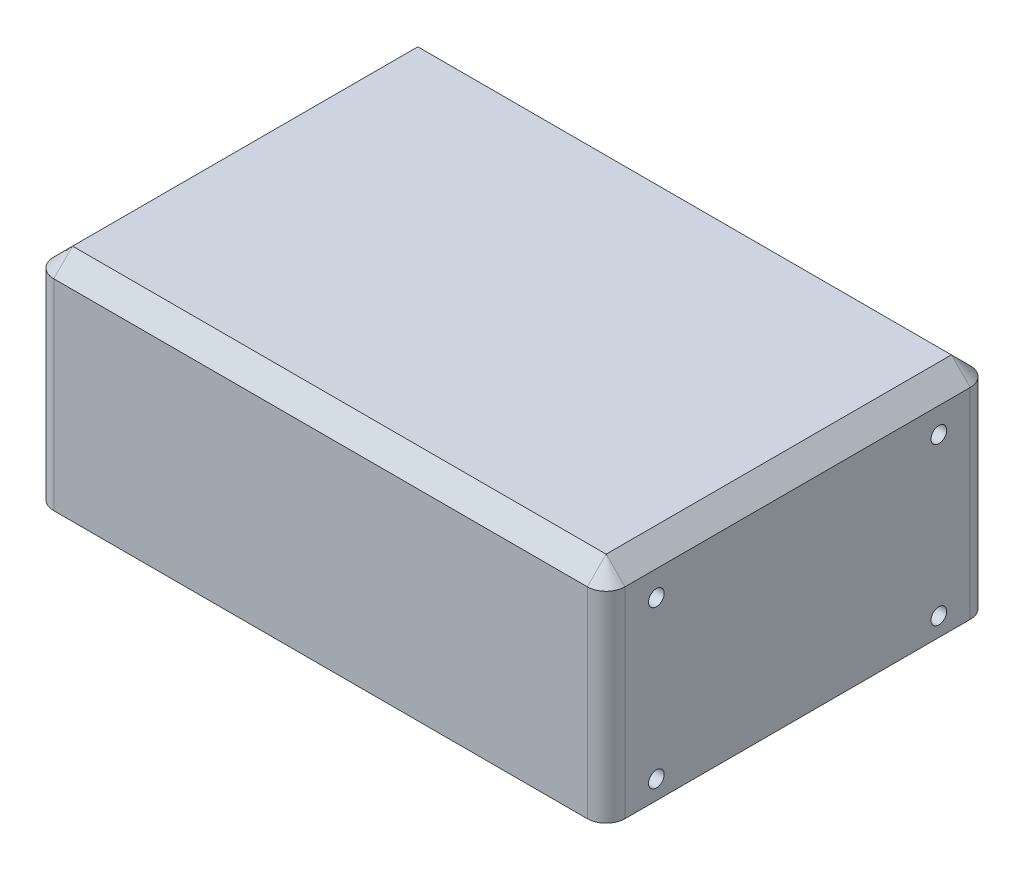
SolidWorks part; units mm, degrees
material "6063-T83"
ref_plane "Front Plane" through (0, 0, 0) normal (0, 0, 1) x (1, 0, 0)
ref_plane "Top Plane" through (0, 0, 0) normal (0, 1, 0) x (1, 0, 0)
ref_plane "Right Plane" through (0, 0, 0) normal (1, 0, 0) x (0, 0, -1)
sketch "Sketch1" plane through (0, 0, 0) normal (0, 1, 0) x (1, 0, 0)
  line L1 (0, 0) -> (-91, 0)
  line L2 (0, 0) -> (0, -61)
  line L3 (0, -61) -> (-91, -61)
  line L4 (-91, 0) -> (-91, -61)
  dimension "D1" = 91
  dimension "D2" = 61
extrude "Boss-Extrude1" add sketch "Sketch1" along normal blind 35
sketch "Sketch2" plane through (0, 0, 0) normal (1, 0, 0) x (0, 0, -1)
  line L0 (-30.5, 35) -> (-30.5, 0) construction
  line L1 (-61, 35) -> (0, 35) construction
  line L2 (-61, 0) -> (0, 0) construction
  line L3 (-8, 28) -> (-8, 3) construction
  circle A0 centre (-8, 28) radius 1.25
  circle A1 centre (-8, 3) radius 1.25
  circle A2 centre (-53, 3) radius 1.25
  circle A3 centre (-53, 28) radius 1.25
  dimension "D1" = 2.5
  dimension "D2" = 2.5
  dimension "D3" = 22.5
  dimension "D4" = 25
  dimension "D5" = 3
extrude "Cut-Extrude1" cut sketch "Sketch2" against normal blind 8
extrude "Cut-Extrude2" cut sketch "Sketch2<2>" along normal blind 8 from surface starting at face at (-91, 17.5, 30.5)
sketch "Sketch2<2>" plane through (0, 0, 0) normal (1, 0, 0) x (0, 0, -1) same geometry as "Sketch2"
fillet "Fillet2" radius 3 4 edges at (-91, 17.5, 0) (0, 17.5, 0) (0, 17.5, 61) (-91, 17.5, 61)
chamfer "Chamfer1" distance 3 angle 45 8 edges at (-45.5, 35, 61) (-0.8787, 35, 60.1213) (-90.1213, 35, 60.1213) (0, 35, 30.5) (-91, 35, 30.5) (-0.8787, 35, 0.8787) (-90.1213, 35, 0.8787) (-45.5, 35, 0)
sketch "Sketch3" plane through (0, 0, 0) normal (0, -1, 0) x (1, 0, 0)
  line L0 (-45.5, 44.5) -> (-45.5, 16.5) construction
  line L1 (-91, 3) -> (-91, 58) construction
  line L2 (-3, 0) -> (-88, 0) construction
  line L3 (-88, 61) -> (-3, 61) construction
  line L4 (-3, 0) -> (-88, 0) construction
  line L5 (-88, 61) -> (-3, 61) construction
  line L6 (-3, 0) -> (-3, 61) construction
  line L7 (-3, 30.5) -> (-45.5, 30.5) construction
  circle A0 centre (-45.5, 44.5) radius 1.25
  circle A1 centre (-45.5, 16.5) radius 1.25
  dimension "D1" = 2.5
  dimension "D2" = 2.5
  dimension "D3" = 45.5
  dimension "D4" = 28
extrude "Cut-Extrude3" cut sketch "Sketch3" against normal blind 10
